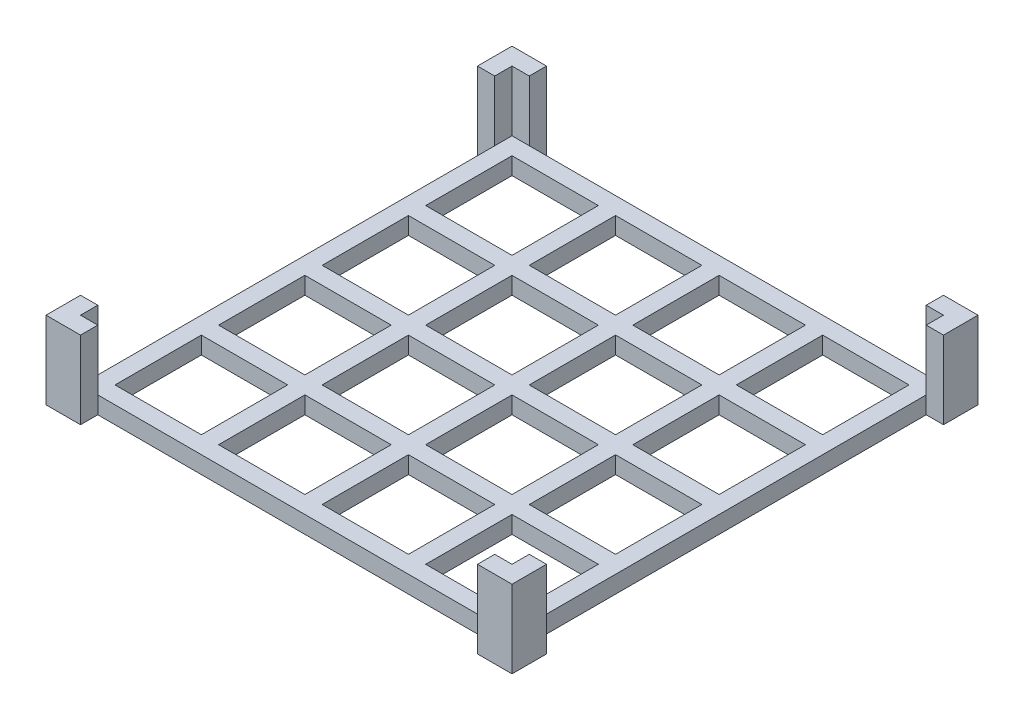
SolidWorks part; units mm, degrees
ref_plane "Front Plane" through (0, 0, 0) normal (0, 0, 1) x (1, 0, 0)
ref_plane "Top Plane" through (0, 0, 0) normal (0, 1, 0) x (1, 0, 0)
ref_plane "Right Plane" through (0, 0, 0) normal (1, 0, 0) x (0, 0, -1)
sketch "Sketch1" plane through (0, 0, 0) normal (0, 1, 0) x (1, 0, 0)
  line L0 (0, 0) -> (-49.3047, 0) construction
  line L1 (-42, 31) -> (-42, 33)
  line L2 (-42, 33) -> (-46, 33)
  line L3 (-46, 33) -> (-46, 29)
  line L4 (-46, 29) -> (-44, 29)
  line L5 (-44, 29) -> (-44, 31)
  line L6 (4, 33) -> (4, 31)
  line L7 (4, 31) -> (6, 31)
  line L8 (6, 29) -> (8, 29)
  line L9 (-8, 5) -> (-18, 5) construction
  line L10 (-8, 7) -> (-15.8633, 7) construction
  line L11 (-8, 17) -> (-14.8417, 17) construction
  line L12 (-8, -5) -> (-16.8168, -5) construction
  line L13 (-8, 29) -> (-13.8882, 29) construction
  line L14 (-8, 19) -> (-12, 19) construction
  line L15 (-8, -7) -> (-15.1823, -7) construction
  line L16 (-8, -17) -> (-14.6374, -17) construction
  line L17 (8, 29) -> (8, 33)
  line L18 (-42, 29) -> (-32, 29)
  line L19 (-42, 29) -> (-42, 19)
  line L20 (-42, 19) -> (-32, 19)
  line L21 (-32, 29) -> (-32, 19)
  line L22 (-30, 29) -> (-20, 29)
  line L23 (-30, 29) -> (-30, 19)
  line L24 (-30, 19) -> (-20, 19)
  line L25 (-20, 29) -> (-20, 19)
  line L26 (-18, 29) -> (-8, 29)
  line L27 (-18, 29) -> (-18, 19)
  line L28 (-18, 19) -> (-8, 19)
  line L29 (-8, 29) -> (-8, 19)
  line L30 (-6, 29) -> (4, 29)
  line L31 (-6, 29) -> (-6, 19)
  line L32 (-6, 19) -> (4, 19)
  line L33 (4, 29) -> (4, 19)
  line L34 (-32, 17) -> (-42, 17)
  line L35 (-32, 17) -> (-32, 7)
  line L36 (-32, 7) -> (-42, 7)
  line L37 (-42, 17) -> (-42, 7)
  line L38 (-30, 17) -> (-20, 17)
  line L39 (-30, 17) -> (-30, 7)
  line L40 (-30, 7) -> (-20, 7)
  line L41 (-20, 17) -> (-20, 7)
  line L42 (-18, 7) -> (-8, 7)
  line L43 (-18, 7) -> (-18, 17)
  line L44 (-18, 17) -> (-8, 17)
  line L45 (-8, 7) -> (-8, 17)
  line L46 (-6, 17) -> (4, 17)
  line L47 (-6, 17) -> (-6, 7)
  line L48 (-6, 7) -> (4, 7)
  line L49 (4, 17) -> (4, 7)
  line L50 (-6, 5) -> (4, 5)
  line L51 (-6, 5) -> (-6, -5)
  line L52 (-6, -5) -> (4, -5)
  line L53 (4, 5) -> (4, -5)
  line L54 (-18, -5) -> (-8, -5)
  line L55 (-18, -5) -> (-18, 5)
  line L56 (-18, 5) -> (-8, 5)
  line L57 (-8, -5) -> (-8, 5)
  line L58 (-20, 5) -> (-30, 5)
  line L59 (-20, 5) -> (-20, -5)
  line L60 (-20, -5) -> (-30, -5)
  line L61 (-30, 5) -> (-30, -5)
  line L62 (-32, -5) -> (-42, -5)
  line L63 (-32, -5) -> (-32, 5)
  line L64 (-32, 5) -> (-42, 5)
  line L65 (-42, -5) -> (-42, 5)
  line L66 (-42, -7) -> (-32, -7)
  line L67 (-42, -7) -> (-42, -17)
  line L68 (-42, -17) -> (-32, -17)
  line L69 (-32, -7) -> (-32, -17)
  line L70 (-30, -7) -> (-20, -7)
  line L71 (-30, -7) -> (-30, -17)
  line L72 (-30, -17) -> (-20, -17)
  line L73 (-20, -7) -> (-20, -17)
  line L74 (-18, -7) -> (-8, -7)
  line L75 (-18, -7) -> (-18, -17)
  line L76 (-18, -17) -> (-8, -17)
  line L77 (-8, -7) -> (-8, -17)
  line L78 (-6, -7) -> (4, -7)
  line L79 (-6, -7) -> (-6, -17)
  line L80 (-6, -17) -> (4, -17)
  line L81 (4, -7) -> (4, -17)
  line L82 (-44, 31) -> (6, 31)
  line L83 (-44, 31) -> (-44, -19)
  line L84 (-44, -19) -> (6, -19)
  line L85 (6, 31) -> (6, -19)
  line L86 (8, 33) -> (4, 33)
  line L87 (4, -19) -> (4, -21)
  line L88 (4, -21) -> (8, -21)
  line L89 (8, -21) -> (8, -17)
  line L90 (8, -17) -> (6, -17)
  line L91 (6, -17) -> (6, -19)
  line L92 (-42, -21) -> (-46, -21)
  line L93 (-46, -21) -> (-46, -17)
  line L94 (-46, -17) -> (-44, -17)
  line L95 (-44, -17) -> (-44, -19)
  line L96 (-42, -19) -> (-42, -21)
  point P1 (-12, 12)
  point P3 (-12, 0)
  point P8 (-24, 0)
  point P10 (0, 24)
  point P11 (-24, 12)
  point P12 (0, 12)
  point P13 (0, -12)
  point P14 (-12, -12)
  point P16 (-24, -12)
  point P19 (-36, 12)
  point P21 (-36, 24)
  point P22 (-24, 24)
  point P23 (-12, 24)
  point P24 (-36, 0)
  point P25 (-36, -12)
  point P32 (8, 29)
  point P34 (4, 33)
  point P35 (8, 33)
  point P36 (-46, -19)
  point P37 (-46, -21)
  point P38 (-42, -21)
  point P39 (4, -21)
  point P40 (8, -21)
  point P41 (8, -17)
  line B0 (-0.1035, 1.9813) -> (-3.7918, 1.315)
  line B1 (-3.7918, -1.315) -> (-0.1035, -1.9813)
  arc B2 (-3.9397, 1.2764) -> (-3.9397, -1.2764) centre (-3.5, 0) ccw
  arc B3 (0.1486, 1.9945) -> (0.1486, -1.9945) centre (0, 0) cw
  arc B4 (-3.9397, 1.2764) -> (-3.7918, 1.315) centre (-3.614, 0.3309) cw
  arc B5 (-3.7918, -1.315) -> (-3.9397, -1.2764) centre (-3.614, -0.3309) cw
  arc B6 (0.1486, 1.9945) -> (-0.1035, 1.9813) centre (0.0743, 0.9972) ccw
  arc B7 (0.1486, -1.9945) -> (-0.1035, -1.9813) centre (0.0743, -0.9972) cw
  line B8 (-12.1035, 1.9813) -> (-15.7918, 1.315)
  line B9 (-15.7918, -1.315) -> (-12.1035, -1.9813)
  arc B10 (-15.9397, 1.2764) -> (-15.9397, -1.2764) centre (-15.5, 0) ccw
  arc B11 (-11.8514, 1.9945) -> (-11.8514, -1.9945) centre (-12, 0) cw
  arc B12 (-15.9397, 1.2764) -> (-15.7918, 1.315) centre (-15.614, 0.3309) cw
  arc B13 (-15.7918, -1.315) -> (-15.9397, -1.2764) centre (-15.614, -0.3309) cw
  arc B14 (-11.8514, 1.9945) -> (-12.1035, 1.9813) centre (-11.9257, 0.9972) ccw
  arc B15 (-11.8514, -1.9945) -> (-12.1035, -1.9813) centre (-11.9257, -0.9972) cw
  line B16 (-24.1035, 1.9813) -> (-27.7918, 1.315)
  line B17 (-27.7918, -1.315) -> (-24.1035, -1.9813)
  arc B18 (-27.9397, 1.2764) -> (-27.9397, -1.2764) centre (-27.5, 0) ccw
  arc B19 (-23.8514, 1.9945) -> (-23.8514, -1.9945) centre (-24, 0) cw
  arc B20 (-27.9397, 1.2764) -> (-27.7918, 1.315) centre (-27.614, 0.3309) cw
  arc B21 (-27.7918, -1.315) -> (-27.9397, -1.2764) centre (-27.614, -0.3309) cw
  arc B22 (-23.8514, 1.9945) -> (-24.1035, 1.9813) centre (-23.9257, 0.9972) ccw
  arc B23 (-23.8514, -1.9945) -> (-24.1035, -1.9813) centre (-23.9257, -0.9972) cw
  line B24 (-0.1035, 13.9813) -> (-3.7918, 13.315)
  line B25 (-3.7918, 10.685) -> (-0.1035, 10.0187)
  arc B26 (-3.9397, 13.2764) -> (-3.9397, 10.7236) centre (-3.5, 12) ccw
  arc B27 (0.1486, 13.9945) -> (0.1486, 10.0055) centre (0, 12) cw
  arc B28 (-3.9397, 13.2764) -> (-3.7918, 13.315) centre (-3.614, 12.3309) cw
  arc B29 (-3.7918, 10.685) -> (-3.9397, 10.7236) centre (-3.614, 11.6691) cw
  arc B30 (0.1486, 13.9945) -> (-0.1035, 13.9813) centre (0.0743, 12.9972) ccw
  arc B31 (0.1486, 10.0055) -> (-0.1035, 10.0187) centre (0.0743, 11.0028) cw
  line B32 (-12.1035, 13.9813) -> (-15.7918, 13.315)
  line B33 (-15.7918, 10.685) -> (-12.1035, 10.0187)
  arc B34 (-15.9397, 13.2764) -> (-15.9397, 10.7236) centre (-15.5, 12) ccw
  arc B35 (-11.8514, 13.9945) -> (-11.8514, 10.0055) centre (-12, 12) cw
  arc B36 (-15.9397, 13.2764) -> (-15.7918, 13.315) centre (-15.614, 12.3309) cw
  arc B37 (-15.7918, 10.685) -> (-15.9397, 10.7236) centre (-15.614, 11.6691) cw
  arc B38 (-11.8514, 13.9945) -> (-12.1035, 13.9813) centre (-11.9257, 12.9972) ccw
  arc B39 (-11.8514, 10.0055) -> (-12.1035, 10.0187) centre (-11.9257, 11.0028) cw
  line B40 (-24.1035, 13.9813) -> (-27.7918, 13.315)
  line B41 (-27.7918, 10.685) -> (-24.1035, 10.0187)
  arc B42 (-27.9397, 13.2764) -> (-27.9397, 10.7236) centre (-27.5, 12) ccw
  arc B43 (-23.8514, 13.9945) -> (-23.8514, 10.0055) centre (-24, 12) cw
  arc B44 (-27.9397, 13.2764) -> (-27.7918, 13.315) centre (-27.614, 12.3309) cw
  arc B45 (-27.7918, 10.685) -> (-27.9397, 10.7236) centre (-27.614, 11.6691) cw
  arc B46 (-23.8514, 13.9945) -> (-24.1035, 13.9813) centre (-23.9257, 12.9972) ccw
  arc B47 (-23.8514, 10.0055) -> (-24.1035, 10.0187) centre (-23.9257, 11.0028) cw
  line B48 (-12.1035, -10.0187) -> (-15.7918, -10.685)
  line B49 (-15.7918, -13.315) -> (-12.1035, -13.9813)
  arc B50 (-15.9397, -10.7236) -> (-15.9397, -13.2764) centre (-15.5, -12) ccw
  arc B51 (-11.8514, -10.0055) -> (-11.8514, -13.9945) centre (-12, -12) cw
  arc B52 (-15.9397, -10.7236) -> (-15.7918, -10.685) centre (-15.614, -11.6691) cw
  arc B53 (-15.7918, -13.315) -> (-15.9397, -13.2764) centre (-15.614, -12.3309) cw
  arc B54 (-11.8514, -10.0055) -> (-12.1035, -10.0187) centre (-11.9257, -11.0028) ccw
  arc B55 (-11.8514, -13.9945) -> (-12.1035, -13.9813) centre (-11.9257, -12.9972) cw
  line B56 (-0.1035, -10.0187) -> (-3.7918, -10.685)
  line B57 (-3.7918, -13.315) -> (-0.1035, -13.9813)
  arc B58 (-3.9397, -10.7236) -> (-3.9397, -13.2764) centre (-3.5, -12) ccw
  arc B59 (0.1486, -10.0055) -> (0.1486, -13.9945) centre (0, -12) cw
  arc B60 (-3.9397, -10.7236) -> (-3.7918, -10.685) centre (-3.614, -11.6691) cw
  arc B61 (-3.7918, -13.315) -> (-3.9397, -13.2764) centre (-3.614, -12.3309) cw
  arc B62 (0.1486, -10.0055) -> (-0.1035, -10.0187) centre (0.0743, -11.0028) ccw
  arc B63 (0.1486, -13.9945) -> (-0.1035, -13.9813) centre (0.0743, -12.9972) cw
  line B64 (-24.1035, -10.0187) -> (-27.7918, -10.685)
  line B65 (-27.7918, -13.315) -> (-24.1035, -13.9813)
  arc B66 (-27.9397, -10.7236) -> (-27.9397, -13.2764) centre (-27.5, -12) ccw
  arc B67 (-23.8514, -10.0055) -> (-23.8514, -13.9945) centre (-24, -12) cw
  arc B68 (-27.9397, -10.7236) -> (-27.7918, -10.685) centre (-27.614, -11.6691) cw
  arc B69 (-27.7918, -13.315) -> (-27.9397, -13.2764) centre (-27.614, -12.3309) cw
  arc B70 (-23.8514, -10.0055) -> (-24.1035, -10.0187) centre (-23.9257, -11.0028) ccw
  arc B71 (-23.8514, -13.9945) -> (-24.1035, -13.9813) centre (-23.9257, -12.9972) cw
  line B72 (-0.1035, 25.9813) -> (-3.7918, 25.315)
  line B73 (-3.7918, 22.685) -> (-0.1035, 22.0187)
  arc B74 (-3.9397, 25.2764) -> (-3.9397, 22.7236) centre (-3.5, 24) ccw
  arc B75 (0.1486, 25.9945) -> (0.1486, 22.0055) centre (0, 24) cw
  arc B76 (-3.9397, 25.2764) -> (-3.7918, 25.315) centre (-3.614, 24.3309) cw
  arc B77 (-3.7918, 22.685) -> (-3.9397, 22.7236) centre (-3.614, 23.6691) cw
  arc B78 (0.1486, 25.9945) -> (-0.1035, 25.9813) centre (0.0743, 24.9972) ccw
  arc B79 (0.1486, 22.0055) -> (-0.1035, 22.0187) centre (0.0743, 23.0028) cw
  line B80 (-12.1035, 25.9813) -> (-15.7918, 25.315)
  line B81 (-15.7918, 22.685) -> (-12.1035, 22.0187)
  arc B82 (-15.9397, 25.2764) -> (-15.9397, 22.7236) centre (-15.5, 24) ccw
  arc B83 (-11.8514, 25.9945) -> (-11.8514, 22.0055) centre (-12, 24) cw
  arc B84 (-15.9397, 25.2764) -> (-15.7918, 25.315) centre (-15.614, 24.3309) cw
  arc B85 (-15.7918, 22.685) -> (-15.9397, 22.7236) centre (-15.614, 23.6691) cw
  arc B86 (-11.8514, 25.9945) -> (-12.1035, 25.9813) centre (-11.9257, 24.9972) ccw
  arc B87 (-11.8514, 22.0055) -> (-12.1035, 22.0187) centre (-11.9257, 23.0028) cw
  line B88 (-24.1035, 25.9813) -> (-27.7918, 25.315)
  line B89 (-27.7918, 22.685) -> (-24.1035, 22.0187)
  arc B90 (-27.9397, 25.2764) -> (-27.9397, 22.7236) centre (-27.5, 24) ccw
  arc B91 (-23.8514, 25.9945) -> (-23.8514, 22.0055) centre (-24, 24) cw
  arc B92 (-27.9397, 25.2764) -> (-27.7918, 25.315) centre (-27.614, 24.3309) cw
  arc B93 (-27.7918, 22.685) -> (-27.9397, 22.7236) centre (-27.614, 23.6691) cw
  arc B94 (-23.8514, 25.9945) -> (-24.1035, 25.9813) centre (-23.9257, 24.9972) ccw
  arc B95 (-23.8514, 22.0055) -> (-24.1035, 22.0187) centre (-23.9257, 23.0028) cw
  line B96 (-36.1035, -10.0187) -> (-39.7918, -10.685)
  line B97 (-39.7918, -13.315) -> (-36.1035, -13.9813)
  arc B98 (-39.9397, -10.7236) -> (-39.9397, -13.2764) centre (-39.5, -12) ccw
  arc B99 (-35.8514, -10.0055) -> (-35.8514, -13.9945) centre (-36, -12) cw
  arc B100 (-39.9397, -10.7236) -> (-39.7918, -10.685) centre (-39.614, -11.6691) cw
  arc B101 (-39.7918, -13.315) -> (-39.9397, -13.2764) centre (-39.614, -12.3309) cw
  arc B102 (-35.8514, -10.0055) -> (-36.1035, -10.0187) centre (-35.9257, -11.0028) ccw
  arc B103 (-35.8514, -13.9945) -> (-36.1035, -13.9813) centre (-35.9257, -12.9972) cw
  line B104 (-36.1035, 25.9813) -> (-39.7918, 25.315)
  line B105 (-39.7918, 22.685) -> (-36.1035, 22.0187)
  arc B106 (-39.9397, 25.2764) -> (-39.9397, 22.7236) centre (-39.5, 24) ccw
  arc B107 (-35.8514, 25.9945) -> (-35.8514, 22.0055) centre (-36, 24) cw
  arc B108 (-39.9397, 25.2764) -> (-39.7918, 25.315) centre (-39.614, 24.3309) cw
  arc B109 (-39.7918, 22.685) -> (-39.9397, 22.7236) centre (-39.614, 23.6691) cw
  arc B110 (-35.8514, 25.9945) -> (-36.1035, 25.9813) centre (-35.9257, 24.9972) ccw
  arc B111 (-35.8514, 22.0055) -> (-36.1035, 22.0187) centre (-35.9257, 23.0028) cw
  line B112 (-36.1035, 1.9813) -> (-39.7918, 1.315)
  line B113 (-39.7918, -1.315) -> (-36.1035, -1.9813)
  arc B114 (-39.9397, 1.2764) -> (-39.9397, -1.2764) centre (-39.5, 0) ccw
  arc B115 (-35.8514, 1.9945) -> (-35.8514, -1.9945) centre (-36, 0) cw
  arc B116 (-39.9397, 1.2764) -> (-39.7918, 1.315) centre (-39.614, 0.3309) cw
  arc B117 (-39.7918, -1.315) -> (-39.9397, -1.2764) centre (-39.614, -0.3309) cw
  arc B118 (-35.8514, 1.9945) -> (-36.1035, 1.9813) centre (-35.9257, 0.9972) ccw
  arc B119 (-35.8514, -1.9945) -> (-36.1035, -1.9813) centre (-35.9257, -0.9972) cw
  line B120 (-36.1035, 13.9813) -> (-39.7918, 13.315)
  line B121 (-39.7918, 10.685) -> (-36.1035, 10.0187)
  arc B122 (-39.9397, 13.2764) -> (-39.9397, 10.7236) centre (-39.5, 12) ccw
  arc B123 (-35.8514, 13.9945) -> (-35.8514, 10.0055) centre (-36, 12) cw
  arc B124 (-39.9397, 13.2764) -> (-39.7918, 13.315) centre (-39.614, 12.3309) cw
  arc B125 (-39.7918, 10.685) -> (-39.9397, 10.7236) centre (-39.614, 11.6691) cw
  arc B126 (-35.8514, 13.9945) -> (-36.1035, 13.9813) centre (-35.9257, 12.9972) ccw
  arc B127 (-35.8514, 10.0055) -> (-36.1035, 10.0187) centre (-35.9257, 11.0028) cw
sketch_block_instance "Block1-4"
sketch_block "Block1"
sketch_block_instance "Block1-6"
sketch_block_instance "Block1-7"
sketch_block_instance "Block1-8"
sketch_block_instance "Block1-9"
sketch_block_instance "Block1-10"
sketch_block_instance "Block1-14"
sketch_block_instance "Block1-15"
sketch_block_instance "Block1-16"
sketch_block_instance "Block1-17"
sketch_block_instance "Block1-18"
sketch_block_instance "Block1-19"
sketch_block_instance "Block1-20"
sketch_block_instance "Block1-21"
sketch_block_instance "Block1-22"
sketch_block_instance "Block1-23"
extrude "Boss-Extrude16" add sketch "Sketch1" along normal blind 9 from offset 2 contours L17 L86 L6 L7 L85 L8 | L89 L90 L85 L84 L87 L88 | L96 L84 L83 L94 L93 L92 | L5 L82 L1 L2 L3 L4 region at (-44.3333, 0, -31.3333) region at (6.3333, 0, -31.3333) region at (-44.3333, 0, 19.3333) region at (6.3333, 0, 19.3333)
extrude "Boss-Extrude17" add sketch "Sketch1<28>" along normal blind 2 from offset 2 contours L85 L7 L82 L5 L83 L84 L74 L77 L76 L75 L66 L69 L68 L67 L50 L53 L52 L51 L38 L41 L40 L39 L37 L34 L35 L36 L26 L29 L28 L27 L18 L21 L20 L19 L22 L25 L24 region at (-19, 0, -6)
sketch "Sketch1<28>" plane through (0, 0, 0) normal (0, 1, 0) x (1, 0, 0) same geometry as "Sketch1"
